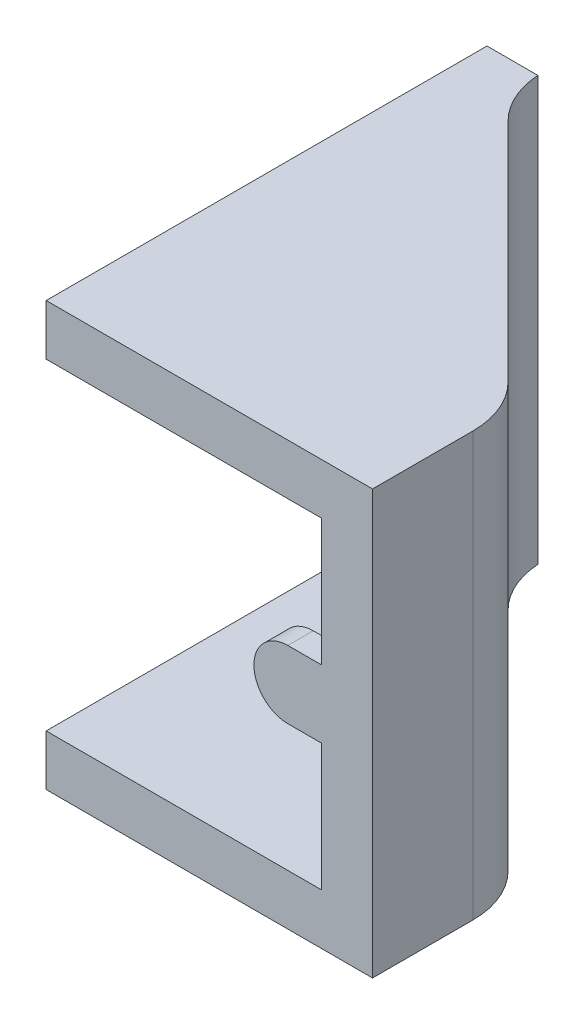
SolidWorks part; units mm, degrees
ref_plane "前视基准面" through (0, 0, 0) normal (0, 0, 1) x (1, 0, 0)
ref_plane "上视基准面" through (0, 0, 0) normal (0, 1, 0) x (1, 0, 0)
ref_plane "右视基准面" through (0, 0, 0) normal (1, 0, 0) x (0, 0, -1)
sketch "草图1" plane through (0, 0, 0) normal (0, 0, 1) x (1, 0, 0)
  line L1 (0, 0) -> (10, 0)
  line L2 (0, 0) -> (0, -15)
  line L3 (0, -15) -> (10, -15)
  line L4 (10, 0) -> (10, -15)
  dimension "D1" = 10
  dimension "D2" = 15
extrude "凸台-拉伸1" add sketch "草图1" along normal blind 3
sketch "草图2" plane through (0, 0, 3) normal (0, 0, 1) x (1, 0, 0)
  line L0 (0, -15) -> (10, -15) construction
  line L1 (7, 5) -> (10, 5)
  line L2 (7, 5) -> (7, -20)
  line L3 (7, -20) -> (10, -20)
  line L4 (10, 5) -> (10, -20)
  line L5 (10, -15) -> (10, 0) construction
  dimension "D1" = 3
  dimension "D2" = 25
  dimension "D3" = 5
  dimension "D4" = 3
extrude "凸台-拉伸2" add sketch "草图2" along normal blind 6
sketch "草图3" plane through (0, -20, 0) normal (0, -1, 0) x (-1, 0, 0)
  line L0 (-10, -9) -> (-23.2635, -22.2635)
  line L1 (-23.2635, -29.0208) -> (-23.2635, -22.2635)
  line L2 (-26.2635, -21.0208) -> (-10, -4.7574)
  line L3 (-10, -9) -> (-10, -3) construction
  line L4 (-10, -4.7574) -> (-10, -9)
  line L5 (-26.2635, -21.0208) -> (-26.2635, -29.0208)
  line L6 (-26.2635, -29.0208) -> (-23.2635, -29.0208)
  dimension "D1" = 23
  dimension "D2" = 3
  dimension "D3" = 3
  dimension "D4" = 8
extrude "凸台-拉伸3" add sketch "草图3" against normal blind 25
sketch "草图4" plane through (0, -20, 0) normal (0, -1, 0) x (-1, 0, 0)
  line L0 (-7, -9) -> (-10, -9)
  line L1 (-10, -9) -> (-23.2635, -22.2635)
  line L2 (-23.2635, -22.2635) -> (-23.2635, -29.0208)
  line L3 (-23.2635, -29.0208) -> (-7, -29.0208)
  line L4 (-7, -29.0208) -> (-7, -9)
extrude "凸台-拉伸4" add sketch "草图4" against normal blind 3
sketch "草图5" plane through (0, 5, 0) normal (0, 1, 0) x (1, 0, 0)
  line L0 (7, -9) -> (10, -9)
  line L1 (10, -9) -> (23.2635, -22.2635)
  line L2 (23.2635, -22.2635) -> (23.2635, -29.0208)
  line L3 (23.2635, -29.0208) -> (7, -29.0208)
  line L4 (7, -29.0208) -> (7, -9)
extrude "凸台-拉伸5" add sketch "草图5" against normal blind 3
fillet "圆角1" radius 5 1 edges at (26.2635, -7.5, 21.0208)
sketch "草图6" plane through (0, 0, 0) normal (0, 0, -1) x (-1, 0, 0)
  line L1 (-10, 0) -> (0, 0)
  line L2 (-10, 0) -> (-10, -15)
  line L3 (-10, -15) -> (0, -15)
  line L4 (0, 0) -> (0, -15)
extrude "切除-拉伸1" cut sketch "草图6" against normal blind 3
fillet "圆角2" radius 5 1 edges at (10, -7.5, 4.7574)
sketch "草图7" plane through (23.2635, 0, 0) normal (-1, 0, 0) x (0, 0, 1)
  line L0 (29.0208, 2) -> (29.0208, -17) construction
  line L1 (29.0208, -9.5) -> (27.5208, -9.5)
  line L2 (29.0208, -9.5) -> (29.0208, -5.5)
  line L3 (29.0208, -5.5) -> (27.5208, -5.5)
  line L4 (27.5208, -9.5) -> (27.5208, -5.5)
  line L5 (29.0208, 2) -> (22.2635, 2) construction
  line L6 (22.2635, -17) -> (29.0208, -17) construction
  dimension "D1" = 1.5
  dimension "D2" = 7.5
  dimension "D3" = 7.5
extrude "凸台-拉伸6" add sketch "草图7" along normal blind 4
fillet "圆角3" radius 2 2 edges at (19.2635, -9.5, 28.2708) (19.2635, -5.5, 28.2708)
